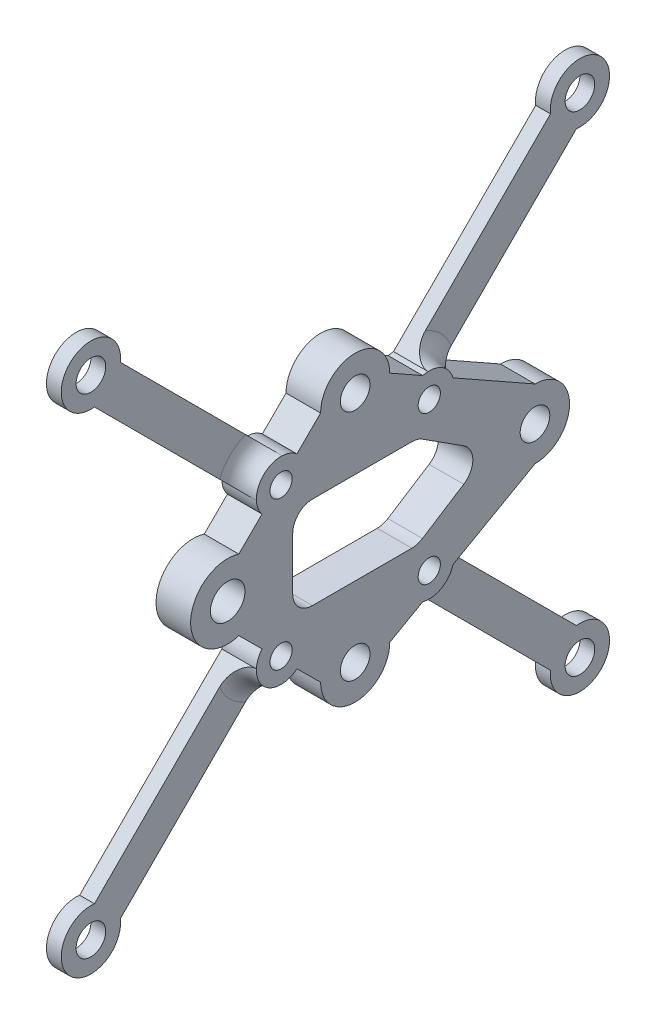
SolidWorks part; units mm, degrees
material "ABS"
ref_plane "Front Plane" through (0, 0, 0) normal (1, 0, 0) x (0, 1, 0)
ref_plane "Top Plane" through (0, 0, 0) normal (0, 0, 1) x (0, 1, 0)
ref_plane "Right Plane" through (0, 0, 0) normal (0, 1, 0) x (-1, 0, 0)
sketch "Sketch1" plane through (0, 0, 0) normal (1, 0, 0) x (0, 1, 0)
  line L0 (-23.6, 0) -> (23.6, 0) construction
  line L1 (0, 0) -> (0, 25.8061) construction
  line L2 (0, 25.8061) -> (0, -36.4) construction
  circle A0 centre (-23.6, 0) radius 3
  circle A1 centre (23.6, 0) radius 3
  circle A2 centre (0, 25.8061) radius 3.5
  circle A3 centre (0, -36.4) radius 3
  circle A4 centre (0, 25.8061) radius 7.5
  circle A5 centre (-23.6, 0) radius 7
  circle A6 centre (0, -36.4) radius 7
  circle A7 centre (23.6, 0) radius 7
  point P18 (0, 25.8061)
  dimension "D2" = 25.8061
  dimension "D3" = 6
  dimension "D4" = 6
  dimension "D5" = 7
  dimension "D7" = 6
  dimension "D1" = 47.2
  dimension "D6" = 62.2061
  dimension "D8" = 4
extrude "Boss-Extrude1" add sketch "Sketch1" along normal blind 13.6
sketch "Sketch2" plane through (13.6, 0, 0) normal (1, 0, 0) x (0, 1, 0)
  line L0 (-7.1532, 23.5517) -> (-23.6, 7)
  line L1 (-23.6, -7) -> (-7, -36.4)
  line L2 (7, -36.4) -> (23.6, -7)
  line L3 (23.6, 7) -> (7.1532, 23.5517)
  circle A2 centre (0, 25.8061) radius 7.5 construction
  circle A3 centre (-23.6, 0) radius 7 construction
  circle A4 centre (0, -36.4) radius 7 construction
  circle A5 centre (23.6, 0) radius 7 construction
  arc A6 (23.6, 7) -> (23.6, -7) centre (23.6, 0) ccw
  arc A7 (7, -36.4) -> (-7, -36.4) centre (0, -36.4) ccw
  arc A8 (-23.6, -7) -> (-23.6, 7) centre (-23.6, 0) ccw
  arc A9 (-7.1532, 23.5517) -> (7.1532, 23.5517) centre (0, 25.8061) ccw
extrude "Boss-Extrude2" add sketch "Sketch2" against normal up to surface (13.6 mm away) up to face at (0, -23.6, -7)
sketch "Sketch3" plane through (13.6, 0, 0) normal (1, 0, 0) x (0, 1, 0)
  circle A0 centre (15, 15) radius 2.25
  circle A1 centre (15, -15) radius 2.25
  circle A2 centre (-15, -15) radius 2.25
  circle A3 centre (-15, 15) radius 2.25
  point P0 (0, 0)
  dimension "D3" = 4.5
  dimension "D4" = 4.5
  dimension "D5" = 4.5
  dimension "D6" = 4.5
  dimension "D1" = 30
  dimension "D2" = 30
extrude "Cut-Extrude1" cut sketch "Sketch3" against normal blind 27.6
sketch "Sketch4" plane through (13.6, 0, 0) normal (1, 0, 0) x (0, 1, 0)
  circle A0 centre (-15, 15) radius 5
  circle A1 centre (15, 15) radius 5
  circle A2 centre (15, -15) radius 5
  circle A3 centre (-15, -15) radius 5
  circle A4 centre (-15, 15) radius 2.25
  circle A5 centre (15, 15) radius 2.25
  circle A6 centre (15, -15) radius 2.25
  circle A7 centre (-15, -15) radius 2.25
  dimension "D1" = 10
  dimension "D2" = 10
  dimension "D3" = 10
  dimension "D4" = 10
extrude "Boss-Extrude3" add sketch "Sketch4" against normal up to surface (13.6 mm away) up to face at (0, -15, -17.25)
sketch "Sketch5" plane through (0, 0, 0) normal (1, 0, 0) x (0, 1, 0)
  line L0 (-9.3322, -12.6384) -> (0, -27.2452)
  line L1 (-9.3322, 12.6384) -> (9.3322, 12.6384)
  line L2 (-9.3322, 12.6384) -> (-9.3322, -12.6384)
  line L4 (9.3322, 12.6384) -> (9.3322, -12.6384)
  line L7 (9.3322, -12.6384) -> (0, -27.2452)
  point P0 (0, 0)
extrude "Cut-Extrude2" cut sketch "Sketch5" along normal blind 32.6
fillet "Fillet1" radius 4 5 edges at (6.8, 0, -27.2452) (6.8, 9.3322, -12.6384) (6.8, -9.3322, -12.6384) (6.8, 9.3322, 12.6384) (6.8, -9.3322, 12.6384)
sketch "Sketch6" plane through (0, 0, 0) normal (-1, 0, 0) x (0, -1, 0)
  line L0 (18.5355, 18.5355) -> (49.4975, 49.4975) construction
  line L1 (18.5355, -18.5355) -> (49.4975, -49.4975) construction
  line L2 (-51.756, 47.5229) -> (-52.1138, 46.8812)
  line L3 (-46.8812, 52.1138) -> (-47.3762, 51.6188)
  line L4 (46.8812, 52.1138) -> (47.3762, 51.6188)
  line L5 (14.7617, 19.9943) -> (46.8812, 52.1138)
  line L6 (52.1138, 46.8812) -> (51.6188, 47.3762)
  line L7 (46.8812, -52.1138) -> (47.3762, -51.6188)
  line L8 (52.1138, -46.8812) -> (51.6188, -47.3762)
  line L9 (-52.1138, -46.8812) -> (-51.6188, -47.3762)
  line L10 (-46.8812, -52.1138) -> (-47.3762, -51.6188)
  line L11 (-15.7213, -20.9539) -> (-46.8812, -52.1138)
  line L12 (-19.9943, 14.7617) -> (-52.1138, 46.8812)
  line L14 (23.6, 7) -> (18.8366, 11.7937)
  line L15 (11.8182, 18.8569) -> (7.1532, 23.5517)
  line L16 (-7.1532, 23.5517) -> (-11.8182, 18.8569)
  line L17 (-18.8366, 11.7937) -> (-23.6, 7)
  line L18 (-23.6, -7) -> (-19.8245, -13.6868)
  line L19 (-16.3675, -19.8094) -> (-7, -36.4)
  line L20 (7, -36.4) -> (16.3675, -19.8094)
  line L21 (19.8245, -13.6868) -> (23.6, -7)
  line L27 (-16.3675, -19.8094) -> (-15.7213, -20.9539)
  line L28 (15.7213, -20.9539) -> (16.3675, -19.8094)
  line L30 (-18.5355, 18.5355) -> (-49.4975, 49.4975) construction
  line L32 (-2.6163, 2.6163) -> (46.8812, 52.1138) construction
  line L33 (0, 0) -> (49.4975, 49.4975) construction
  line L36 (15.7213, -20.9539) -> (46.8812, -52.1138)
  line L38 (-18.5355, -18.5355) -> (-49.4975, -49.4975) construction
  line L40 (-19.9943, -14.7617) -> (-52.1138, -46.8812)
  line L42 (-14.7617, 19.9943) -> (-46.8812, 52.1138)
  line L44 (19.9943, 14.7617) -> (52.1138, 46.8812)
  line L46 (19.9943, -14.7617) -> (52.1138, -46.8812)
  line L48 (0, 0) -> (-2.6163, 2.6163) construction
  line L49 (0, 0) -> (-2.6163, -2.6163) construction
  arc A0 (-51.756, 47.5229) -> (-47.3762, 51.6188) centre (-49.4975, 49.4975) ccw
  arc A1 (47.3762, 51.6188) -> (51.6188, 47.3762) centre (49.4975, 49.4975) ccw
  arc A2 (51.6188, -47.3762) -> (47.3762, -51.6188) centre (49.4975, -49.4975) ccw
  arc A3 (-47.3762, -51.6188) -> (-51.6188, -47.3762) centre (-49.4975, -49.4975) ccw
  arc A8 (18.8366, 11.7937) -> (11.8182, 18.8569) centre (15, 15) ccw
  arc A9 (7.1532, 23.5517) -> (-7.1532, 23.5517) centre (0, 25.8061) ccw
  arc A10 (-11.8182, 18.8569) -> (-18.8366, 11.7937) centre (-15, 15) ccw
  arc A11 (-23.6, 7) -> (-23.6, -7) centre (-23.6, 0) ccw
  arc A12 (-19.8245, -13.6868) -> (-16.3675, -19.8094) centre (-15, -15) ccw
  arc A13 (-7, -36.4) -> (7, -36.4) centre (0, -36.4) ccw
  arc A14 (16.3675, -19.8094) -> (19.8245, -13.6868) centre (15, -15) ccw
  arc A15 (23.6, -7) -> (23.6, 7) centre (23.6, 0) ccw
  arc A16 (19.9943, 14.7617) -> (14.7617, 19.9943) centre (15, 15) ccw
  arc A18 (-14.7617, 19.9943) -> (-19.9943, 14.7617) centre (-15, 15) ccw
  arc A20 (-19.9943, -14.7617) -> (-16.3675, -19.8094) centre (-15, -15) ccw
  arc A22 (16.3675, -19.8094) -> (19.9943, -14.7617) centre (15, -15) ccw
  point P6 (67.0007, 67.0007)
  dimension "D3" = 6
  dimension "D6" = 6
  dimension "D7" = 6
  dimension "D8" = 6
  dimension "D1" = 70
  dimension "D4" = 3.7
  dimension "D5" = 0
  dimension "D2" = 4
extrude "Boss-Extrude4" add sketch "Sketch6" against normal blind 3
fillet "Fillet2" radius 4 4 edges at (3, 19.0605, -17.9176) (3, 18.5355, 18.5355) (3, -19.0605, -17.9176) (3, -18.5355, 18.5355)
sketch "Sketch7" plane through (13.6, 0, 0) normal (1, 0, 0) x (0, 1, 0)
  line L8 (-18.8366, 11.7937) -> (-23.6, 7)
  line L9 (-23.6, -7) -> (-19.8245, -13.6868)
  line L10 (-16.3675, -19.8094) -> (-7, -36.4)
  line L11 (7, -36.4) -> (16.3675, -19.8094)
  line L12 (19.8245, -13.6868) -> (23.6, -7)
  line L13 (23.6, 7) -> (18.8366, 11.7937)
  line L14 (11.8182, 18.8569) -> (7.1532, 23.5517)
  line L15 (-7.1532, 23.5517) -> (-11.8182, 18.8569)
  line L16 (-18.8366, 11.7937) -> (-23.6, 7)
  line L17 (-23.6, -7) -> (-19.8245, -13.6868)
  line L18 (-16.3675, -19.8094) -> (-7, -36.4)
  line L19 (7, -36.4) -> (16.3675, -19.8094)
  line L20 (19.8245, -13.6868) -> (23.6, -7)
  line L21 (23.6, 7) -> (18.8366, 11.7937)
  line L22 (11.8182, 18.8569) -> (7.1532, 23.5517)
  line L23 (-7.1532, 23.5517) -> (-11.8182, 18.8569)
  arc A8 (-11.8182, 18.8569) -> (-18.8366, 11.7937) centre (-15, 15) ccw
  arc A9 (-23.6, 7) -> (-23.6, -7) centre (-23.6, 0) ccw
  arc A10 (-19.8245, -13.6868) -> (-16.3675, -19.8094) centre (-15, -15) ccw
  arc A11 (-7, -36.4) -> (7, -36.4) centre (0, -36.4) ccw
  arc A12 (16.3675, -19.8094) -> (19.8245, -13.6868) centre (15, -15) ccw
  arc A13 (23.6, -7) -> (23.6, 7) centre (23.6, 0) ccw
  arc A14 (18.8366, 11.7937) -> (11.8182, 18.8569) centre (15, 15) ccw
  arc A15 (7.1532, 23.5517) -> (-7.1532, 23.5517) centre (0, 25.8061) ccw
  arc A16 (-11.8182, 18.8569) -> (-18.8366, 11.7937) centre (-15, 15) ccw
  arc A17 (-23.6, 7) -> (-23.6, -7) centre (-23.6, 0) ccw
  arc A18 (-19.8245, -13.6868) -> (-16.3675, -19.8094) centre (-15, -15) ccw
  arc A19 (-7, -36.4) -> (7, -36.4) centre (0, -36.4) ccw
  arc A20 (16.3675, -19.8094) -> (19.8245, -13.6868) centre (15, -15) ccw
  arc A21 (23.6, -7) -> (23.6, 7) centre (23.6, 0) ccw
  arc A22 (18.8366, 11.7937) -> (11.8182, 18.8569) centre (15, 15) ccw
  arc A23 (7.1532, 23.5517) -> (-7.1532, 23.5517) centre (0, 25.8061) ccw
  dimension "D1" = 0
extrude "Cut-Extrude4" cut sketch "Sketch7" against normal up to vertex (6.6 mm away) up to point (7, -16.3675, -19.8094)
sketch "Sketch9" plane through (3, 0, 0) normal (1, 0, 0) x (0, 1, 0)
  circle A0 centre (-49.4975, 49.4975) radius 3
  circle A1 centre (-49.4975, 49.4975) radius 6
  circle A2 centre (49.4975, 49.4975) radius 6
  circle A3 centre (49.4975, 49.4975) radius 3
  circle A4 centre (49.4975, -49.4975) radius 6
  circle A5 centre (49.4975, -49.4975) radius 3
  circle A6 centre (-49.4975, -49.4975) radius 6
  circle A7 centre (-49.4975, -49.4975) radius 3
  dimension "D1" = 3
  dimension "D2" = 4
extrude "Boss-Extrude5" add sketch "Sketch9" against normal up to surface (3 mm away) up to face at (0, 0.0037, 0.2465)
